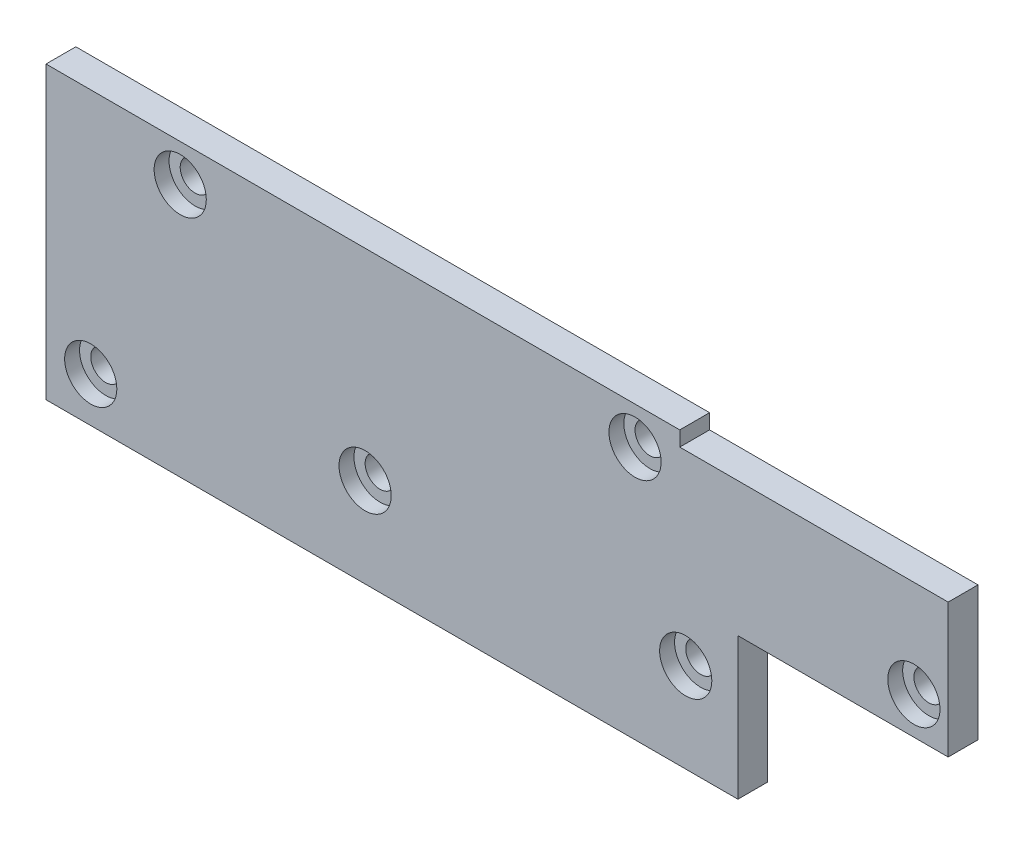
SolidWorks part; units mm, degrees
ref_plane "前视基准面" through (0, 0, 0) normal (0, 0, 1) x (1, 0, 0)
ref_plane "上视基准面" through (0, 0, 0) normal (0, 1, 0) x (1, 0, 0)
ref_plane "右视基准面" through (0, 0, 0) normal (1, 0, 0) x (0, 0, -1)
other "Configuration Table"
sketch "草图1" plane through (0, 0, 0) normal (0, 0, 1) x (1, 0, 0)
  line L6 (0, -5) -> (36.5, -5)
  line L11 (0, -5) -> (0, 0)
  line L12 (0, 0) -> (36.5, 0)
  line L13 (36.5, -5) -> (36.5, 0)
  line L14 (36.5, -5) -> (54.5, -5)
  line L15 (36.5, -5) -> (36.5, -1)
  line L16 (36.5, -1) -> (54.5, -1)
  line L17 (54.5, -5) -> (54.5, -1)
  line L18 (0, 0) -> (-6, 0)
  line L19 (0, 0) -> (0, -19.5)
  line L20 (0, -19.5) -> (-6, -19.5)
  line L21 (-6, 0) -> (-6, -19.5)
  line L22 (0, -19.5) -> (36.5, -19.5)
  line L23 (0, -19.5) -> (0, -5)
  line L24 (0, -5) -> (36.5, -5)
  line L25 (36.5, -19.5) -> (36.5, -5)
  line L26 (36.5, -5) -> (40.4, -5)
  line L27 (36.5, -5) -> (36.5, -19.5)
  line L28 (36.5, -19.5) -> (40.4, -19.5)
  line L29 (40.4, -5) -> (40.4, -19.5)
  line L30 (54.5, -5) -> (40.4, -5)
  line L31 (54.5, -5) -> (54.5, -10)
  line L32 (54.5, -10) -> (40.4, -10)
  line L33 (40.4, -5) -> (40.4, -10)
  circle A0 centre (3, -2.5) radius 1.75
  circle A1 centre (3, -2.5) radius 1
  circle A2 centre (33.5, -2.5) radius 1.75
  circle A4 centre (33.5, -2.5) radius 1
  circle A6 centre (-3, -16.5) radius 1
  circle A7 centre (-3, -16.5) radius 1.75
  circle A8 centre (15.4, -13.5) radius 1.75
  circle A9 centre (15.4, -13.5) radius 1
  circle A10 centre (36.9, -13.5) radius 1.75
  circle A11 centre (36.9, -13.5) radius 1
  circle A12 centre (52.2, -7.5) radius 1.75
  circle A13 centre (52.2, -7.5) radius 1
  point P34 (0, 0)
  dimension "D1" = 5
  dimension "D2" = 3
  dimension "D4" = 2
  dimension "D5" = 3
  dimension "D6" = 30.5
  dimension "D3" = 3.5
  dimension "D7" = 2.5
  dimension "D8" = 1
  dimension "D9" = 14
  dimension "D10" = 6
  dimension "D11" = 3
  dimension "D12" = 3
  dimension "D13" = 3.9
  dimension "D14" = 5
  dimension "D15" = 18
extrude "凸台-拉伸1" add sketch "草图1" along normal blind 2 contours L12 | L18 L21 L20 L19 L11 A7 | L22 L25 L6 L19 | L14 L17 L16 L13 | A7 A6 | A8 A9 | A11 L27 A10 | A11 L27 A10 | A10 L25 L28 L29 L14 | L32 L31 L14 L29 A12 | A12 A13 | L12 L13 L6 L11 | A1 | A4 region at (-3, -9.1452, 0) region at (18.1858, -12.2184, 0) region at (45.5, -3, 0) region at (38.5753, -12.0961, 0) region at (46.6993, -7.5, 0) region at (37.9613, -12.1606, 0) region at (35.8418, -13.5, 0) region at (-4.7005, -16.5, 0) region at (13.6995, -13.5, 0) region at (50.4995, -7.5, 0)
extrude "切除-拉伸2" cut sketch "草图1<8>" against normal blind 1 from surface contours A12 A13 | A0 | A2 | A7 | A8 | A10 region at (50.4995, -7.5, 0) starting at face at (31.35, -7.625, 2)
sketch "草图1<8>" plane through (0, 0, 0) normal (0, 0, 1) x (1, 0, 0) same geometry as "草图1"
